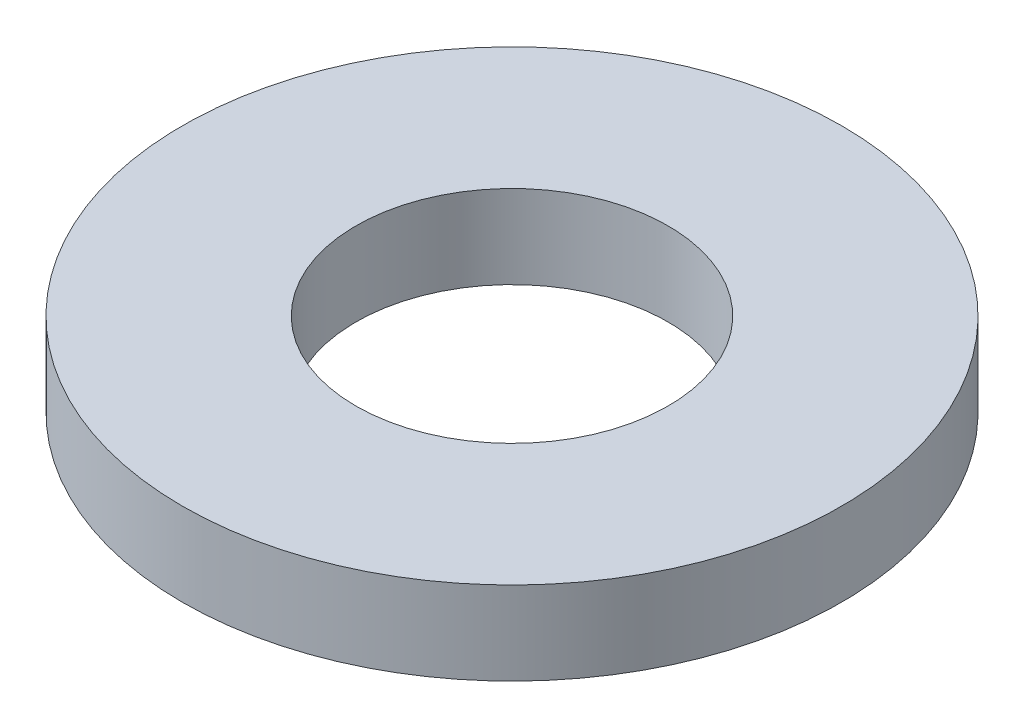
SolidWorks part; units mm, degrees
ref_plane "Front Plane" through (0, 0, 0) normal (0, 0, 1) x (1, 0, 0)
ref_plane "Top Plane" through (0, 0, 0) normal (0, 1, 0) x (1, 0, 0)
ref_plane "Right Plane" through (0, 0, 0) normal (1, 0, 0) x (0, 0, -1)
sketch "Sketch1" plane through (0, 0, 0) normal (0, 1, 0) x (1, 0, 0)
  circle A0 centre (0, 0) radius 47.5
  dimension "FLANGE_OD" = 95
extrude "Boss-Extrude1" add sketch "Sketch1" along normal blind 12
sketch "Sketch2" plane through (0, 0, 0) normal (0, 1, 0) x (1, 0, 0)
  circle A0 centre (0, 0) radius 22.5
  dimension "BORE_D" = 45
extrude "Cut-Extrude1" cut sketch "Sketch2" along normal through all
sketch "Sketch3" plane through (0, 12, 0) normal (0, 1, 0) x (1, 0, 0)
  circle A0 centre (0, 0) radius 17.8103 construction
  circle A1 centre (-17.8103, 0) radius 1.6803
  dimension "BOLT_D" = 3.3606
  dimension "BOLT_PCD" = 35.6207
extrude "Cut-Extrude2" cut sketch "Sketch3" against normal blind 7.9665 rebuild error yes
pattern_circular "CirPattern1" count 6 over 360 rebuild error yes
